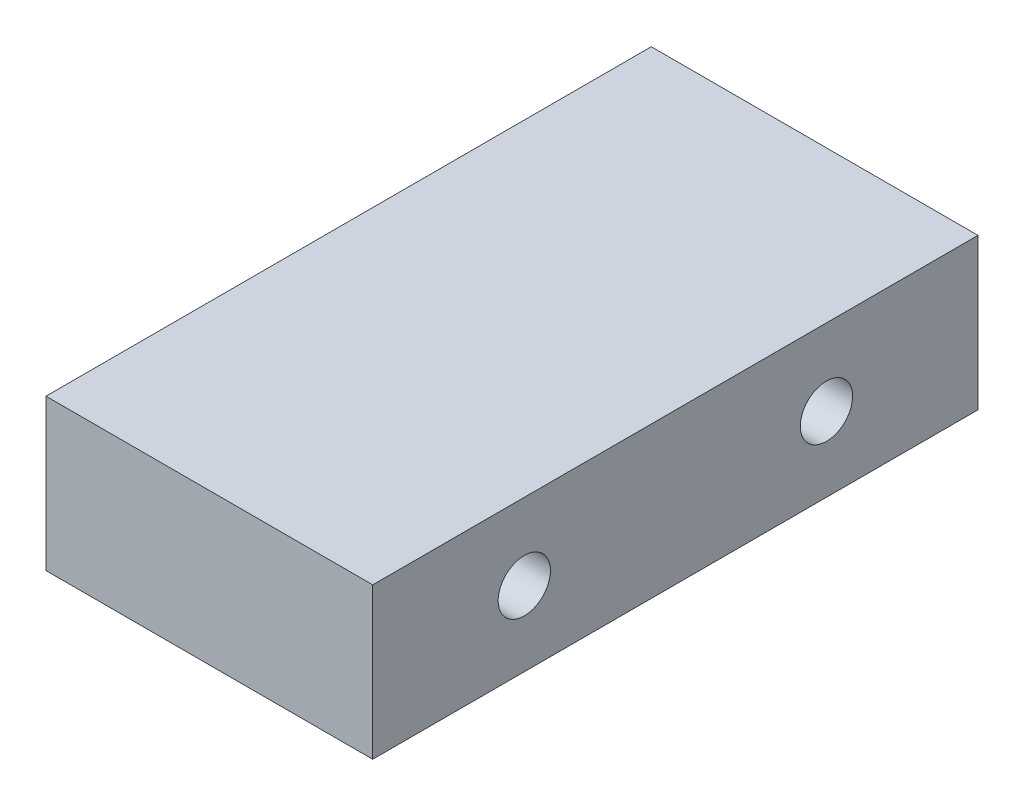
SolidWorks part; units mm, degrees
material "1060 Alloy"
ref_plane "Front Plane" through (0, 0, 0) normal (0, 0, 1) x (1, 0, 0)
ref_plane "Top Plane" through (0, 0, 0) normal (0, 1, 0) x (1, 0, 0)
ref_plane "Right Plane" through (0, 0, 0) normal (1, 0, 0) x (0, 0, -1)
sketch "Sketch1" plane through (0, 0, 0) normal (0, 0, 1) x (1, 0, 0)
  line L0 (-3.18, 0) -> (3.18, 0)
  line L1 (3.18, 0) -> (3.18, 10.34)
  line L2 (3.18, 10.34) -> (17.43, 10.34)
  line L3 (17.43, 10.34) -> (17.43, 19.87)
  line L4 (17.43, 19.87) -> (-3.18, 19.87)
  line L5 (-3.18, 19.87) -> (-3.18, 0)
  line L6 (0, 0) -> (0, 19.87) construction
  dimension "D1" = 9.53
  dimension "D2" = 6.36
  dimension "D3" = 19.87
  dimension "D4" = 20.61
extrude "Boss-Extrude1" add sketch "Sketch1" along normal blind 19.09 and the other way blind 19.09
sketch "Sketch2" plane through (3.18, 0, 0) normal (1, 0, 0) x (0, 0, -1)
  line L0 (19.09, 10.34) -> (6.31, 0)
  line L1 (19.09, 0) -> (-19.09, 0) construction
  line L2 (6.31, 0) -> (19.09, 0)
  line L3 (19.09, 0) -> (19.09, 10.34)
  line L4 (-19.09, 10.34) -> (-19.09, 0)
  line L5 (-19.09, 0) -> (-6.31, 0)
  line L6 (-6.31, 0) -> (-19.09, 10.34)
  line L7 (0, 0) -> (0, 10.34) construction
  line L8 (19.09, 10.34) -> (-19.09, 10.34) construction
  dimension "D1" = 12.62
extrude "Cut-Extrude1" cut sketch "Sketch2" against normal through all
sketch "Sketch3" plane through (0, 0, 0) normal (0, -1, 0) x (1, 0, 0)
  circle A0 centre (0, 0) radius 1.125
  dimension "D1" = 2.25
extrude "Cut-Extrude2" cut sketch "Sketch3" against normal blind 6.35
sketch "Sketch4" plane through (17.43, 0, 0) normal (1, 0, 0) x (0, 0, -1)
  line L0 (0, 10.34) -> (0, 19.87) construction
  line L1 (19.09, 10.34) -> (-19.09, 10.34) construction
  line L2 (19.09, 19.87) -> (-19.09, 19.87) construction
  line L3 (0, 0) -> (0, 10.34) construction
  line L4 (9.53, 15.045) -> (-9.53, 15.045) construction
  circle A0 centre (9.53, 15.045) radius 1.65
  circle A1 centre (-9.53, 15.045) radius 1.65
  circle A2 centre (9.53, 15.045) radius 2.445 construction
  dimension "D1" = 3.3
extrude "Cut-Extrude3" cut sketch "Sketch4" against normal blind 15
